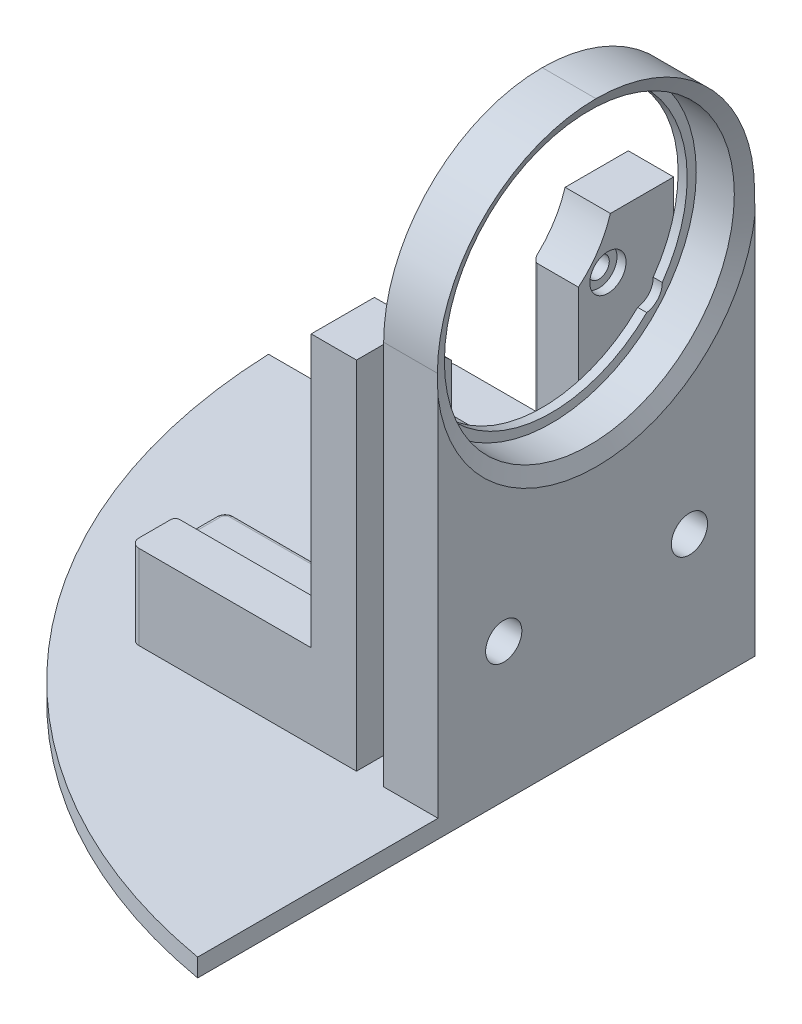
SolidWorks part; units mm, degrees
ref_plane "정면" through (0, 0, 0) normal (0, 0, 1) x (1, 0, 0)
ref_plane "윗면" through (0, 0, 0) normal (0, 1, 0) x (1, 0, 0)
ref_plane "우측면" through (0, 0, 0) normal (1, 0, 0) x (0, 0, -1)
sketch "스케치1" plane through (0, 0, 0) normal (0, 1, 0) x (1, 0, 0)
  line L1 (-11.2423, -2.4904) -> (-64.9523, -2.4904)
  line L2 (-11.2423, -2.4904) -> (-11.2423, -64.0204)
  arc A0 (-64.9523, -2.4904) -> (-11.2423, -64.0204) centre (0, 0) ccw
  dimension "D1" = 130
  dimension "D2" = 53.71
  dimension "D3" = 61.53
extrude "보스-돌출1" add sketch "스케치1" along normal blind 2 contours L1 A0 L2 region at (-33.5169, 0, 27.6158)
sketch "스케치2" plane through (0, 2, 0) normal (0, 1, 0) x (1, 0, 0)
  line L1 (-11.2423, -2.4904) -> (-17.2423, -2.4904)
  line L2 (-11.2423, -2.4904) -> (-11.2423, -37.4904)
  line L3 (-11.2423, -37.4904) -> (-17.2423, -37.4904)
  line L4 (-17.2423, -2.4904) -> (-17.2423, -37.4904)
  dimension "D1" = 35
  dimension "D2" = 6
extrude "보스-돌출2" add sketch "스케치2" along normal blind 60
fillet "필렛1" radius 17.5 2 edges at (-14.2423, 62, 2.4904) (-14.2423, 62, 37.4904)
sketch "스케치3" plane through (-11.2423, 0, 0) normal (1, 0, 0) x (0, 0, -1)
  circle A0 centre (-19.9904, 44.5) radius 16
  dimension "D1" = 32
extrude "컷-돌출1" cut sketch "스케치3" against normal blind 5
chamfer "모따기1" distance 0.8 angle 64 1 edges at (-11.2423, 44.5, 3.9904) first distance on face at (-16.2423, 44.5, 3.9904)
sketch "스케치4" plane through (-16.2423, 0, 0) normal (1, 0, 0) x (0, 0, -1)
  circle A0 centre (-19.9904, 44.5) radius 15
  circle A1 centre (-19.9904, 44.5) radius 16 construction
  dimension "D1" = 1
extrude "컷-돌출2" cut sketch "스케치4" against normal through all
sketch "스케치5" plane through (0, 2, 0) normal (0, 1, 0) x (1, 0, 0)
  line L0 (-17.2423, -2.4904) -> (-64.9523, -2.4904) construction
  line L1 (-20.2423, -2.4904) -> (-45.2423, -2.4904)
  line L2 (-20.2423, -2.4904) -> (-20.2423, -12.9904)
  line L3 (-20.2423, -12.9904) -> (-45.2423, -12.9904)
  line L4 (-45.2423, -2.4904) -> (-45.2423, -12.9904)
  line L5 (-17.2423, -2.4904) -> (-17.2423, -37.4904) construction
  line L6 (-20.2423, -26.9904) -> (-45.2423, -26.9904)
  line L7 (-20.2423, -26.9904) -> (-20.2423, -37.4904)
  line L8 (-20.2423, -37.4904) -> (-45.2423, -37.4904)
  line L9 (-45.2423, -26.9904) -> (-45.2423, -37.4904)
  dimension "D1" = 10.5
  dimension "D2" = 25
  dimension "D3" = 35
  dimension "D4" = 3
extrude "보스-돌출3" add sketch "스케치5" along normal blind 7.3
sketch "스케치6" plane through (0, 9.3, 0) normal (0, 1, 0) x (1, 0, 0)
  line L0 (-45.2423, -32.4904) -> (-25.2423, -32.4904)
  line L1 (-45.2423, -2.4904) -> (-20.2423, -2.4904)
  line L2 (-45.2423, -2.4904) -> (-45.2423, -7.4904)
  line L3 (-25.2423, -12.9904) -> (-20.2423, -12.9904)
  line L4 (-20.2423, -2.4904) -> (-20.2423, -12.9904)
  line L5 (-45.2423, -37.4904) -> (-20.2423, -37.4904)
  line L6 (-45.2423, -37.4904) -> (-45.2423, -32.4904)
  line L7 (-25.2423, -26.9904) -> (-20.2423, -26.9904)
  line L8 (-20.2423, -37.4904) -> (-20.2423, -26.9904)
  line L9 (-45.2423, -7.4904) -> (-25.2423, -7.4904)
  line L10 (-25.2423, -7.4904) -> (-25.2423, -12.9904)
  line L11 (-25.2423, -32.4904) -> (-25.2423, -26.9904)
  line L12 (-45.2423, -12.9904) -> (-20.2423, -12.9904) construction
  line L13 (-45.2423, -26.9904) -> (-20.2423, -26.9904) construction
  line L14 (-25.2423, -37.4904) -> (-25.2423, -26.9904) construction
  line L15 (-45.2423, -32.4904) -> (-20.2423, -32.4904) construction
  line L16 (-25.2423, -2.4904) -> (-25.2423, -12.9904) construction
  line L17 (-45.2423, -7.4904) -> (-20.2423, -7.4904) construction
  dimension "D1" = 5.5
  dimension "D2" = 5.5
  dimension "D3" = 5
  dimension "D4" = 5
extrude "보스-돌출4" add sketch "스케치6" along normal blind 2
fillet "필렛2" radius 1 4 edges at (-45.2423, 6.65, 37.4904) (-45.2423, 5.65, 26.9904) (-45.2423, 5.65, 12.9904) (-45.2423, 6.65, 2.4904)
sketch "스케치7" plane through (-25.2423, 0, 0) normal (-1, 0, 0) x (0, 0, 1)
  line L0 (12.9904, 9.3) -> (12.9904, 2) construction
  line L1 (2.4904, 11.3) -> (12.9904, 11.3)
  line L2 (2.4904, 11.3) -> (2.4904, 41.3)
  line L3 (2.4904, 41.3) -> (9.4661, 41.3)
  line L4 (12.9904, 11.3) -> (12.9904, 36.0147)
  line L5 (37.4904, 11.3) -> (26.9904, 11.3)
  line L6 (37.4904, 11.3) -> (37.4904, 41.3)
  line L7 (37.4904, 41.3) -> (30.5147, 41.3)
  line L8 (26.9904, 11.3) -> (26.9904, 36.0147)
  arc A0 (26.9904, 36.0147) -> (30.5147, 41.3) centre (19.9904, 44.5) ccw
  arc A1 (9.4661, 41.3) -> (12.9904, 36.0147) centre (19.9904, 44.5) ccw
  dimension "D2" = 22
  dimension "D1" = 30
extrude "보스-돌출5" add sketch "스케치7" against normal blind 5
sketch "스케치9" plane through (-25.2423, 0, 0) normal (-1, 0, 0) x (0, 0, 1)
  line L0 (7.4904, 9.3) -> (12.9904, 9.3) construction
  line L1 (9.7404, 35.8) -> (30.2404, 35.8) construction
  line L2 (9.7404, 35.8) -> (9.7404, 15.3) construction
  line L3 (9.7404, 15.3) -> (30.2404, 15.3) construction
  line L4 (30.2404, 35.8) -> (30.2404, 15.3) construction
  circle A0 centre (19.9904, 44.5) radius 15 construction
  circle A1 centre (9.7404, 35.8) radius 1.15
  circle A2 centre (9.7404, 15.3) radius 1.15
  circle A3 centre (30.2404, 15.3) radius 1.15
  circle A4 centre (30.2404, 35.8) radius 1.15
  dimension "D4" = 10.25
  dimension "D5" = 2.3
  dimension "D1" = 20.5
  dimension "D2" = 20.5
  dimension "D3" = 6
extrude "컷-돌출3" cut sketch "스케치9" against normal through all
sketch "스케치10" plane through (-11.2423, 0, 0) normal (1, 0, 0) x (0, 0, -1)
  circle A0 centre (-30.2404, 15.3) radius 2
  circle A1 centre (-9.7404, 15.3) radius 2
  circle A2 centre (-9.7404, 35.8) radius 2
  circle A3 centre (-30.2404, 35.8) radius 2
  dimension "D1" = 4
extrude "컷-돌출4" cut sketch "스케치10" against normal blind 10
fillet "필렛3" radius 0.5 12 edges at (-45.2423, 10.3, 7.4904) (-45.2423, 10.3, 32.4904) (-34.7423, 9.3, 12.9904) (-44.9494, 9.3, 12.6975) (-34.7423, 9.3, 26.9904) (-44.9494, 9.3, 27.2833) (-45.2423, 9.3, 9.7404) (-45.2423, 9.3, 30.2404) (-35.2423, 9.3, 32.4904) (-35.2423, 9.3, 7.4904) (-25.2423, 22.6574, 26.9904) (-25.2423, 22.6574, 12.9904)
